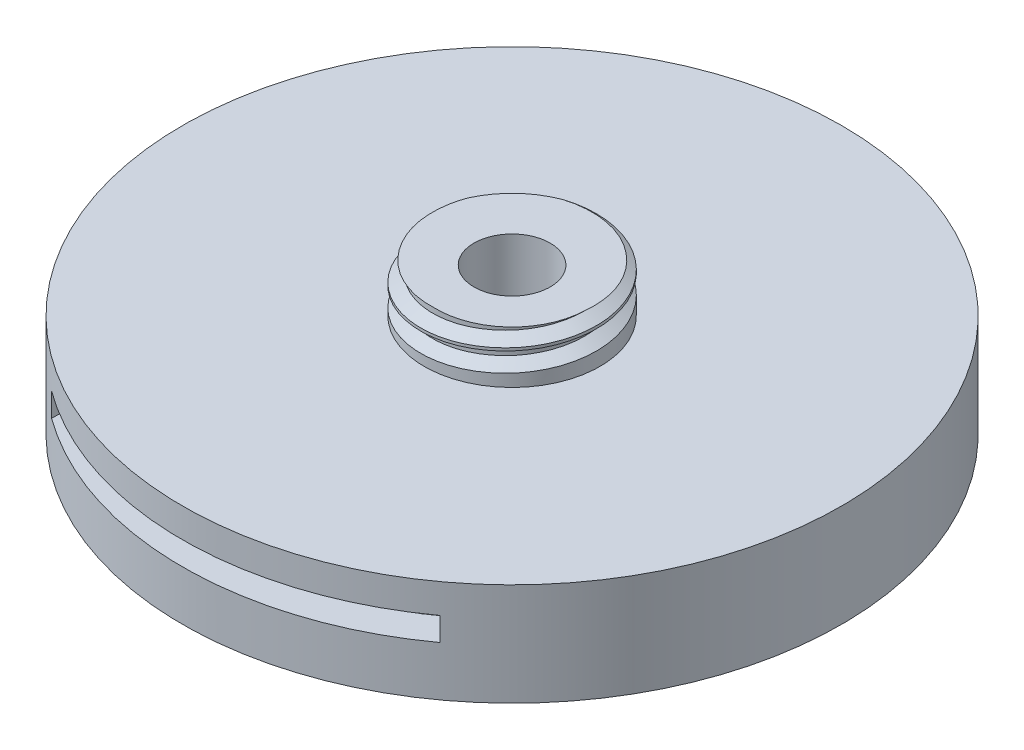
SolidWorks part; units mm, degrees
ref_plane "Ebene vorne" through (0, 0, 0) normal (0, 0, 1) x (1, 0, 0)
ref_plane "Ebene oben" through (0, 0, 0) normal (0, 1, 0) x (1, 0, 0)
ref_plane "Ebene rechts" through (0, 0, 0) normal (1, 0, 0) x (0, 0, -1)
sketch "Skizze1" plane through (0, 0, 0) normal (0, 1, 0) x (1, 0, 0)
  circle A0 centre (-18.0437, 0) radius 5
extrude "Zylinder" add sketch "Skizze1" along normal blind 2.2
ref_plane "Ebene auf Zylinder" through (0, 2.2, 0) normal (0, 1, 0) x (1, 0, 0)
sketch "Skizze4" plane through (0, 2.2, 0) normal (0, 1, 0) x (1, 0, 0)
  circle A0 centre (-18.0437, 0) radius 4.5
extrude "Schnitt-Linear austragen1" cut sketch "Skizze4" against normal blind 5 and the other way blind 10
ref_plane "Eben im Zylinder" through (0, 0.8, 0) normal (0, 1, 0) x (1, 0, 0)
sketch "Skizze5" plane through (0, 0.8, 0) normal (0, 1, 0) x (1, 0, 0)
  circle A0 centre (-18.0437, 0) radius 4.55
ref_plane "Ebene für Aufsatz" through (0, 0, 0) normal (0, -1, 0) x (-1, 0, 0)
sketch "Skizze6" plane through (0, 0, 0) normal (0, -1, 0) x (-1, 0, 0)
  circle A0 centre (18.0437, 0) radius 22.5
extrude "Fassung Objektträgergewinde" add sketch "Skizze6" along normal blind 7
ref_plane "Ebene auf Objektträgerfassung" through (0, -7, 0) normal (0, -1, 0) x (-1, 0, 0)
sketch "Skizze11" plane through (0, -7, 0) normal (0, -1, 0) x (-1, 0, 0)
  circle A0 centre (18.0437, 0) radius 20.3
extrude "Bohrung für Innengewinde" cut sketch "Skizze11" against normal blind 6
sketch "Skizze12" plane through (0, 0, 0) normal (0, -1, 0) x (-1, 0, 0)
  circle A2 centre (18.0437, 0) radius 4.5
ref_plane "Ebene1" through (0, 0, 0) normal (0, -1, 0) x (-1, 0, 0)
sketch "Skizze13" plane through (0, 0, 0) normal (0, -1, 0) x (-1, 0, 0)
  circle A0 centre (18.0437, 0) radius 6
  dimension "D1" = 12
extrude "Aufsatz-Linear austragen1" add sketch "Skizze13" against normal blind 3
ref_plane "Ebene4" through (0, -1, 0) normal (0, -1, 0) x (-1, 0, 0)
sketch "Skizze15" plane through (0, -1, 0) normal (0, -1, 0) x (-1, 0, 0)
  circle A0 centre (18.0437, 0) radius 9.2938
sketch "Skizze16" plane through (0, -7, 0) normal (0, -1, 0) x (-1, 0, 0)
  circle A0 centre (18.0437, 0) radius 2.6
extrude "Schnitt-Linear austragen13" cut sketch "Skizze16" against normal blind 10
thread "Gewinde1" pitch 1.5 method cut profile "Gewindeprofil1" start angle 0, offset 1.6, length 3.5, pitch 1.5, diameter 12
ref_plane "Ebene6" through (-24.0437, 4.6, 0) normal (0, 0, 1) x (-1, 0, 0)
sketch "Gewindeprofil1" plane through (-24.0437, 4.6, 0) normal (0, 0, 1) x (-1, 0, 0)
  line L0 (0, 0) -> (0, 1.5) construction
  line L11 (0, 0) -> (0, 1.3125)
  line L12 (0, 1.3125) -> (-0.8119, 0.8437)
  line L13 (-0.8119, 0.8437) -> (-0.8119, 0.4687)
  line L15 (-0.8119, 0.4687) -> (0, 0)
  line L17 (-0.8119, 0.6562) -> (0, 0.6562) construction
  point P2 (0, 0)
  dimension "Pitch" = 1.5
  dimension "Profile_Angle" = 60
  dimension "Profile_Land" = 0.375
  dimension "Profile_Height" = 0.8119
ref_plane "Ebene7" through (0, -2, 0) normal (0, 1, 0) x (1, 0, 0)
sketch "Skizze17" plane through (0, -2, 0) normal (0, 1, 0) x (1, 0, 0)
  line L1 (-4.7937, -24.7706) -> (-31.2937, -24.7706)
  line L2 (-4.7937, -24.7706) -> (-4.7937, 24.7706)
  line L3 (-4.7937, 24.7706) -> (-31.2937, 24.7706)
  line L4 (-31.2937, -24.7706) -> (-31.2937, 24.7706)
  line L5 (-4.7937, -24.7706) -> (-31.2937, 24.7706) construction
  line L6 (-4.7937, 24.7706) -> (-31.2937, -24.7706) construction
  point P0 (-18.0437, 0)
  dimension "D1" = 26.5
extrude "Schnitt-Linear austragen14" cut sketch "Skizze17" against normal blind 1.6
ref_plane "Ebene für Schrift" through (0, 0, 0) normal (0, 1, 0) x (1, 0, 0)
sketch "Skizze18" plane through (0, 0, 0) normal (0, 1, 0) x (1, 0, 0)
  text T0 "\r\n\r\n5mm" font "Century Gothic" height 3.5
